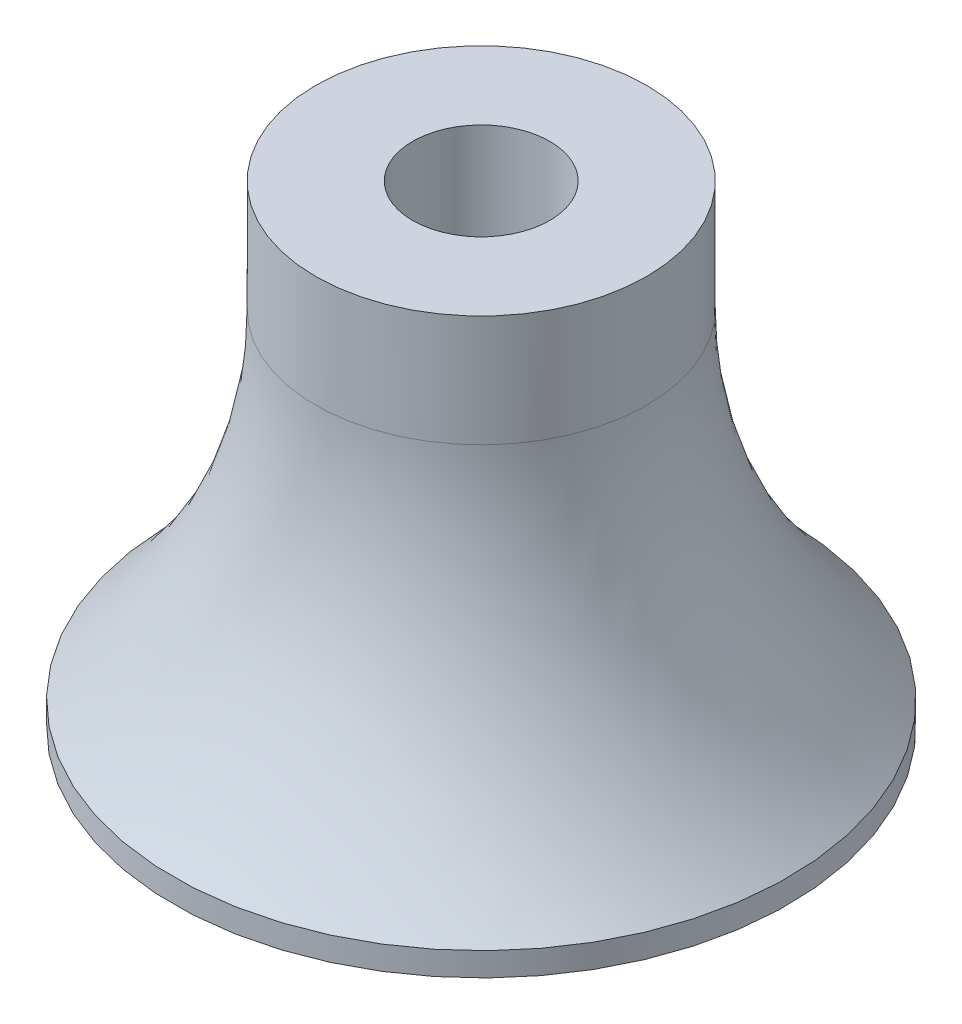
SolidWorks part; units mm, degrees
ref_plane "Front" through (0, 0, 0) normal (0, 0, 1) x (1, 0, 0)
ref_plane "Top" through (0, 0, 0) normal (0, 1, 0) x (1, 0, 0)
ref_plane "Right" through (0, 0, 0) normal (1, 0, 0) x (0, 0, -1)
sketch "Sketch1" plane through (0, 0, 0) normal (0, 1, 0) x (1, 0, 0)
  circle A0 centre (0, 0) radius 1.45
  circle A1 centre (0, 0) radius 3.5
  dimension "D1" = 2.9
  dimension "D2" = 7
extrude "Boss-Extrude1" add sketch "Sketch1" along normal blind 10
sketch "Sketch2" plane through (0, 0, 0) normal (0, -1, 0) x (1, 0, 0)
  circle A0 centre (0, 0) radius 6.5
  circle A1 centre (0, 0) radius 3.5
  circle A2 centre (0, 0) radius 3.5
  circle M3 centre (0, 0) radius 3.5
  circle M4 centre (0, 0) radius 1.45
  dimension "D1" = 0
  dimension "D2" = 3
extrude "Boss-Extrude2" add sketch "Sketch2" against normal blind 0.5 contours M3 M4 | A0 M3 region at (-6.3162, 0, 0) region at (-3.401, 0, 0)
fillet "Fillet1" radius 10 1 edges at (0, 0.5, -3.5)
